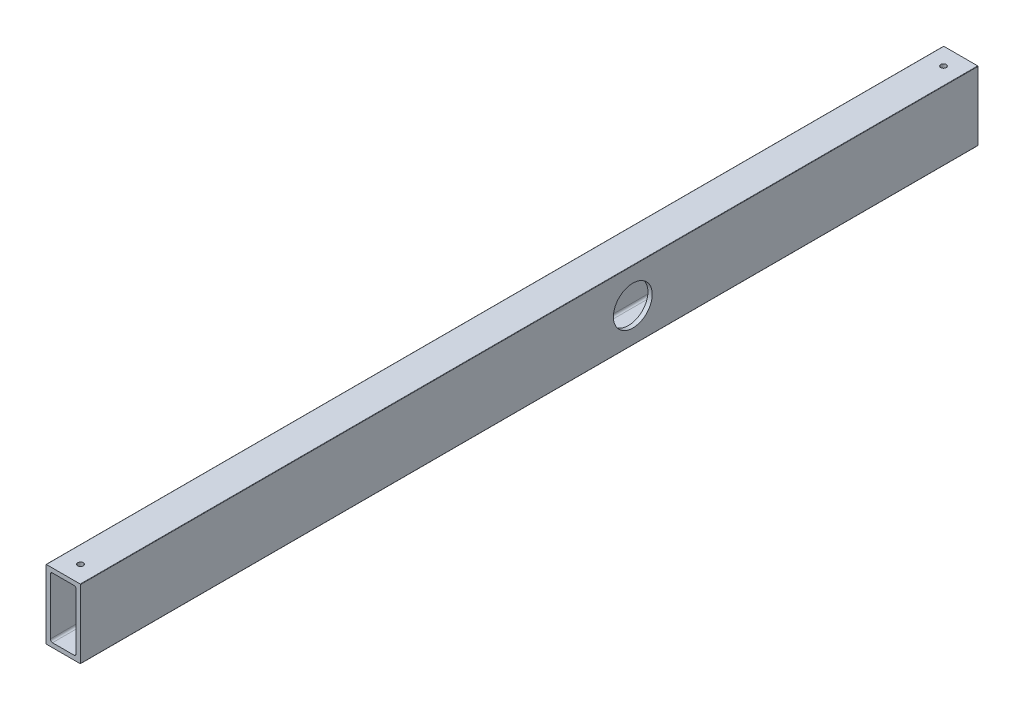
SolidWorks part; units mm, degrees
material "3.0205 (EN-AW 1200)"
ref_plane "Front Plane" through (0, 0, 0) normal (0, 0, 1) x (1, 0, 0)
ref_plane "Top Plane" through (0, 0, 0) normal (0, 1, 0) x (1, 0, 0)
ref_plane "Right Plane" through (0, 0, 0) normal (1, 0, 0) x (0, 0, -1)
ref_plane "Plane1" through (0, 0, 0) normal (0, 0, -1) x (-1, 0, 0)
sketch "Sketch1" plane through (0, 0, 0) normal (0, 0, -1) x (-1, 0, 0)
  line L0 (-3.175, 46.0375) -> (-3.175, 4.7625)
  line L1 (-4.7625, 3.175) -> (-20.6375, 3.175)
  line L2 (-22.225, 4.7625) -> (-22.225, 46.0375)
  line L3 (-20.6375, 47.625) -> (-4.7625, 47.625)
  line L4 (0, 0.254) -> (0, 50.546)
  line L5 (-0.254, 50.8) -> (-25.146, 50.8)
  line L6 (-25.4, 50.546) -> (-25.4, 0.254)
  line L7 (-25.146, 0) -> (-0.254, 0)
  arc A0 (-3.175, 4.7625) -> (-4.7625, 3.175) centre (-4.7625, 4.7625) cw
  arc A1 (-20.6375, 3.175) -> (-22.225, 4.7625) centre (-20.6375, 4.7625) cw
  arc A2 (-22.225, 46.0375) -> (-20.6375, 47.625) centre (-20.6375, 46.0375) cw
  arc A3 (-4.7625, 47.625) -> (-3.175, 46.0375) centre (-4.7625, 46.0375) cw
  arc A4 (-0.254, 0) -> (0, 0.254) centre (-0.254, 0.254) ccw
  arc A5 (0, 50.546) -> (-0.254, 50.8) centre (-0.254, 50.546) ccw
  arc A6 (-25.146, 50.8) -> (-25.4, 50.546) centre (-25.146, 50.546) ccw
  arc A7 (-25.4, 0.254) -> (-25.146, 0) centre (-25.146, 0.254) ccw
extrude "Boss-Extrude1" add sketch "Sketch1" against normal blind 660.4
sketch "Sketch2" plane through (0, 50.8, 0) normal (0, 1, 0) x (1, 0, 0)
  line L0 (0.254, -660.4) -> (25.146, -660.4) construction
  line L1 (25.146, -330.2) -> (0, -330.2) construction
  line L2 (25.146, -660.4) -> (25.146, 0) construction
  line L3 (0, -660.4) -> (0, 0) construction
  circle A0 centre (12.7, -647.7) radius 2.032
  circle A1 centre (12.7, -673.1) radius 2.032
  circle A2 centre (12.7, 12.7) radius 2.032
  circle A3 centre (12.7, -12.7) radius 2.032
  dimension "D1" = 4.064
  dimension "D2" = 4.064
  dimension "D3" = 12.7
  dimension "D4" = 25.4
extrude "Cut-Extrude1" cut sketch "Sketch2" against normal through all
sketch "Sketch5" plane through (25.4, 0, 0) normal (1, 0, 0) x (0, 0, -1)
  line L0 (-660.4, 50.546) -> (0, 50.546) construction
  line L2 (0, 50.546) -> (0, 0.254) construction
  circle A0 centre (-254, 25.146) radius 14.2875
  dimension "D1" = 28.575
  dimension "D2" = 25.4
  dimension "D3" = 254
extrude "Cut-Extrude2" cut sketch "Sketch5" against normal through all
